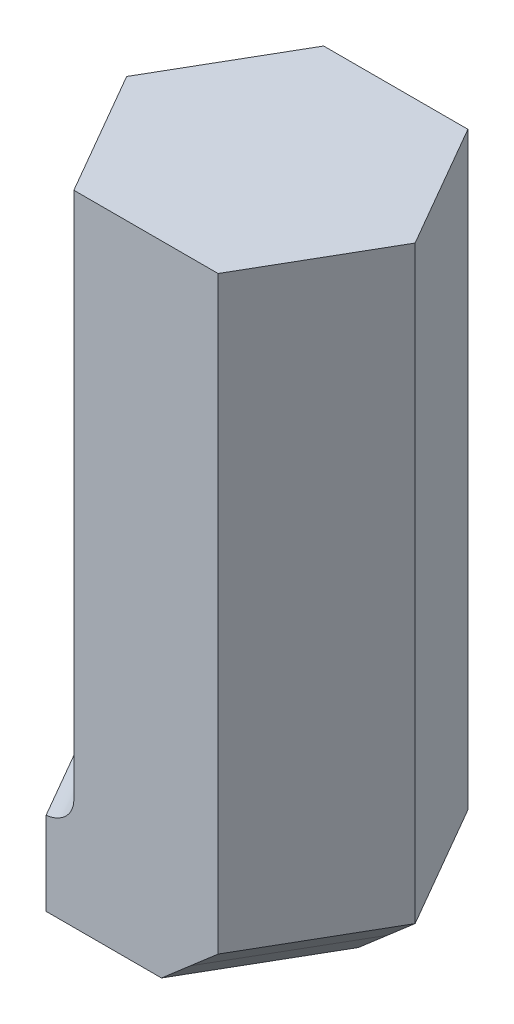
SolidWorks part; units mm, degrees
ref_plane "前视基准面" through (0, 0, 0) normal (0, 0, 1) x (1, 0, 0)
ref_plane "上视基准面" through (0, 0, 0) normal (0, 1, 0) x (1, 0, 0)
ref_plane "右视基准面" through (0, 0, 0) normal (1, 0, 0) x (0, 0, -1)
other "Configuration Table"
sketch "草图1" plane through (0, 0, 0) normal (0, 1, 0) x (1, 0, 0)
  line L1 (2.5981, -4.5) -> (5.1962, 0)
  line L2 (5.1962, 0) -> (2.5981, 4.5)
  line L3 (2.5981, 4.5) -> (-2.5981, 4.5)
  line L4 (-2.5981, 4.5) -> (-5.1962, 0)
  line L5 (-5.1962, 0) -> (-2.5981, -4.5)
  line L6 (-2.5981, -4.5) -> (2.5981, -4.5)
  circle A0 centre (0, 0) radius 4.5 construction
  dimension "D1" = 9
extrude "凸台-拉伸1" add sketch "草图1" along normal blind 20
sketch "草图2" plane through (0, 0, 0) normal (0, -1, 0) x (-1, 0, 0)
  line L0 (-2.5981, 4.5) -> (2.5981, 4.5) construction
  line L1 (6.1962, 0) -> (3.5981, 4.5)
  line L2 (3.5981, 4.5) -> (-1.5981, 4.5)
  line L3 (-1.5981, 4.5) -> (-4.1962, 0)
  line L4 (-4.1962, 0) -> (-1.5981, -4.5)
  line L5 (-1.5981, -4.5) -> (3.5981, -4.5)
  line L6 (3.5981, -4.5) -> (6.1962, 0)
  circle A0 centre (1, 0) radius 4.5 construction
  dimension "D1" = 9
  dimension "D2" = 0
  dimension "D3" = 1
extrude "凸台-拉伸2" add sketch "草图2" along normal blind 3
chamfer "倒角1" distance 2.1 angle 45 2 edges at (2.8971, 0, -2.25) (2.8971, 0, 2.25)
chamfer "倒角2" distance 0.9 angle 45 2 edges at (2.8971, -3, 2.25) (2.8971, -3, -2.25)
fillet "圆角2" radius 1 2 edges at (-3.8971, 0, -2.25) (-3.8971, 0, 2.25)
